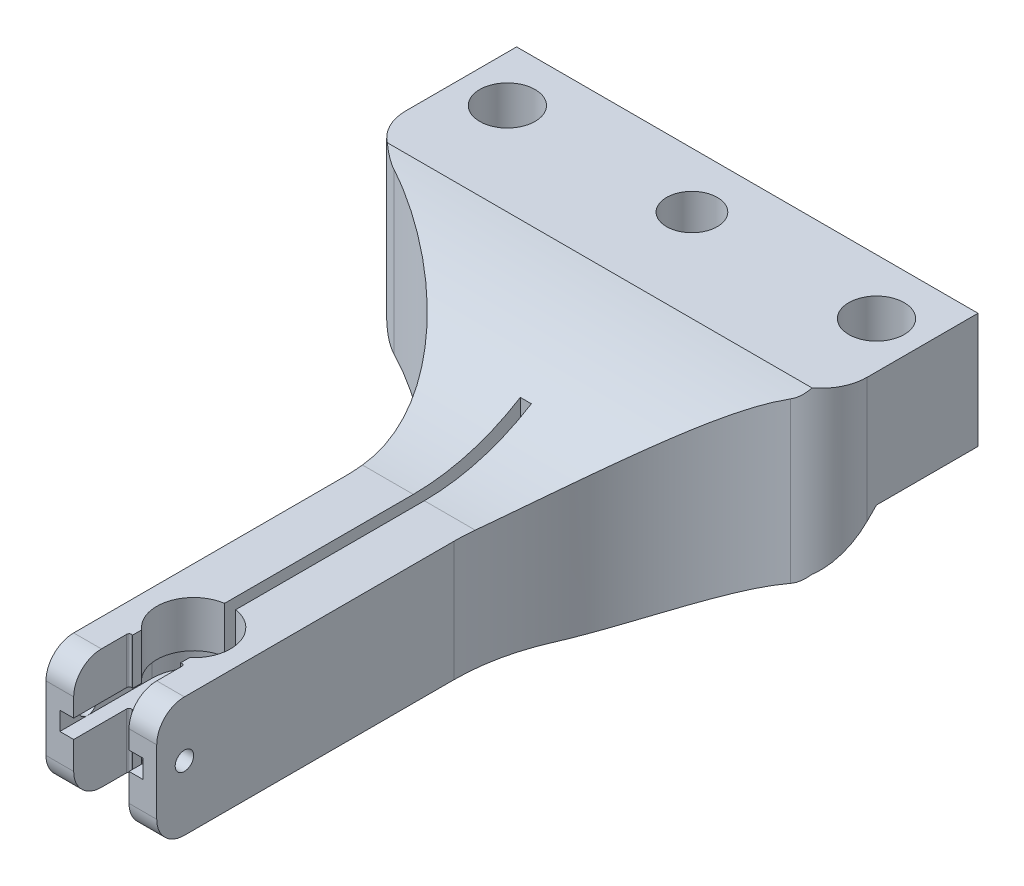
SolidWorks part; units mm, degrees
ref_plane "Front Plane" through (0, 0, 0) normal (0, 0, 1) x (1, 0, 0)
ref_plane "Top Plane" through (0, 0, 0) normal (0, 1, 0) x (1, 0, 0)
ref_plane "Right Plane" through (0, 0, 0) normal (1, 0, 0) x (0, 0, -1)
sketch "Sketch1" plane through (0, 0, 0) normal (0, 1, 0) x (1, 0, 0)
  line L0 (0, 0) -> (0, 54) construction
  line L1 (-20, 54) -> (20, 54) construction
  line L3 (-25, 60) -> (-25, 44)
  line L6 (-25, 60) -> (25, 60)
  line L7 (25, 60) -> (25, 44)
  line L11 (6, 44) -> (25, 44)
  line L12 (-6, 44) -> (-25, 44)
  line L13 (6, 44) -> (6, -10)
  line L14 (6, -10) -> (-6, -10)
  line L15 (-6, -10) -> (-6, 44)
  line L18 (0, 0) -> (0, -10) construction
  circle A1 centre (-20, 54) radius 3
  circle A2 centre (20, 54) radius 3
  circle A3 centre (0, 54) radius 2.75
  point P12 (0, 60)
  point P22 (0, -10)
  dimension "D3" = 10
  dimension "D4" = 16
  dimension "D5" = 6
  dimension "D6" = 6
  dimension "D7" = 5.5
  dimension "D2" = 12
  dimension "D9" = 10
  dimension "D10" = 40
  dimension "D11" = 50
  dimension "D16" = 54
extrude "Boss-Extrude1" add sketch "Sketch1" along normal blind 25 contours L11 L7 L6 L3 L12 A3 A2 A1 region at (0, 0, -35.2999)
fillet "Fillet8" radius 22 2 edges at (6, 12.5, -44) (-6, 12.5, -44)
sketch "Sketch2" plane through (0, 0, 0) normal (0, 1, 0) x (1, 0, 0)
  circle A0 centre (0, 0) radius 4
  dimension "D1" = 8
extrude "Cut-Extrude1" cut sketch "Sketch2" along normal up to surface (25 mm away) up to face at (0, 25, -51.25)
sketch "Sketch4" plane through (0, 0, 0) normal (0, -1, 0) x (-1, 0, 0)
  circle A0 centre (0, 0) radius 4.5
  dimension "D1" = 9
extrude "Cut-Extrude2" cut sketch "Sketch4" against normal blind 2 from offset 6 offset against normal yes
sketch "Sketch5" plane through (0, 25, 0) normal (0, 1, 0) x (1, 0, 0)
  line L0 (0, 36) -> (0, -10) construction
  line L1 (0, 36) -> (-0.6, 36)
  line L2 (-0.6, 36) -> (-0.6, 0)
  line L3 (-0.6, 0) -> (-2.6, 0)
  line L5 (-3, -10) -> (3, -10)
  line L7 (2.6, 0) -> (0.6, 0)
  line L8 (0.6, 0) -> (0.6, 36)
  line L9 (0.6, 36) -> (0, 36)
  line L10 (6, -10) -> (-6, -10) construction
  line L11 (-2.6, 0) -> (-2.6, -4)
  line L12 (-2.6, -4) -> (-3, -4)
  line L13 (-3, -4) -> (-3, -10)
  line L14 (2.6, 0) -> (2.6, -4)
  line L15 (2.6, -4) -> (3, -4)
  line L16 (3, -4) -> (3, -10)
  line L17 (6, -10) -> (-6, -10) construction
  point P2 (0, -10)
  dimension "D1" = 4
  dimension "D2" = 0.6
  dimension "D3" = 3
  dimension "D4" = 2
  dimension "D5" = 36
  dimension "D6" = 2
extrude "Cut-Extrude3" cut sketch "Sketch5" against normal up to surface (25 mm away) up to face at (0, 0, 4)
fillet "Fillet13" radius 0.25 2 edges at (3, 12.5, 4) (-3, 12.5, 4)
sketch "Sketch6" plane through (0, 0, 0) normal (0, 0, 1) x (1, 0, 0)
  line L1 (-4.5, 6) -> (4.5, 6)
  line L2 (-4.5, 6) -> (-4.5, 8)
  line L3 (-4.5, 8) -> (4.5, 8)
  line L4 (4.5, 6) -> (4.5, 8)
extrude "Cut-Extrude4" cut sketch "Sketch6" along normal blind 10
sketch "Sketch8" plane through (-6, 0, 0) normal (-1, 0, 0) x (0, 0, 1)
  line L1 (10, 0) -> (-22.2055, 0) construction
  line L2 (10, 25) -> (10, 0) construction
  circle A0 centre (7, 7) radius 1
  dimension "D1" = 2
  dimension "D2" = 3
  dimension "D3" = 7
extrude "Cut-Extrude5" cut sketch "Sketch8" against normal through all both and the other way through all
sketch "Sketch9" plane through (-25, 0, 0) normal (-1, 0, 0) x (0, 0, 1)
  line L0 (-44, 13) -> (10, 13)
  line L3 (10, 13) -> (10, 25)
  line L4 (10, 25) -> (-44, 25)
  line L5 (-44, 25) -> (-44, 13)
  dimension "D1" = 12
extrude "Cut-Extrude6" cut sketch "Sketch9" against normal up to surface (50 mm away) up to face at (25, 12.5, -52)
fillet "Fillet9" radius 22 1 edges at (0, 13, -44)
sketch "Sketch10" plane through (-25, 0, 0) normal (-1, 0, 0) x (0, 0, 1)
  line L0 (-44, 25) -> (-44, 0) construction
  line L1 (-60, 0) -> (-44, 0)
  line L2 (-60, 0) -> (-60, 12.5)
  line L3 (-60, 12.5) -> (-44, 12.5)
  line L4 (-44, 0) -> (-44, 12.5)
extrude "Cut-Extrude7" cut sketch "Sketch10" against normal up to surface (50 mm away) up to face at (25, 12.5, -52)
fillet "Fillet10" radius 5 1 edges at (0, 12.5, -44) profile chamfer
fillet "Fillet11" radius 15 1 edges at (0, 0, -44)
fillet "Fillet12" radius 5 2 edges at (25, 16.25, -44) (-25, 16.25, -44)
fillet "Fillet7" radius 3 4 edges at (-4.5, 0, 10) (4.5, 0, 10) (-4.5, 13, 10) (4.5, 13, 10)
sketch "Sketch12" plane through (0, -18.25, -18.25) normal (0, -0.7071, -0.7071) x (1, 0, 0)
  line L0 (0, -43.4871) -> (0, -36.416) construction
  line L1 (25, -43.4871) -> (-25, -43.4871) construction
  line L3 (-12.3319, -33.2654) -> (12.3319, -33.2654) construction
  text T0 "Jadhav Lab"
extrude "Boss-Extrude3" add sketch "Sketch12" along normal blind 0.8
